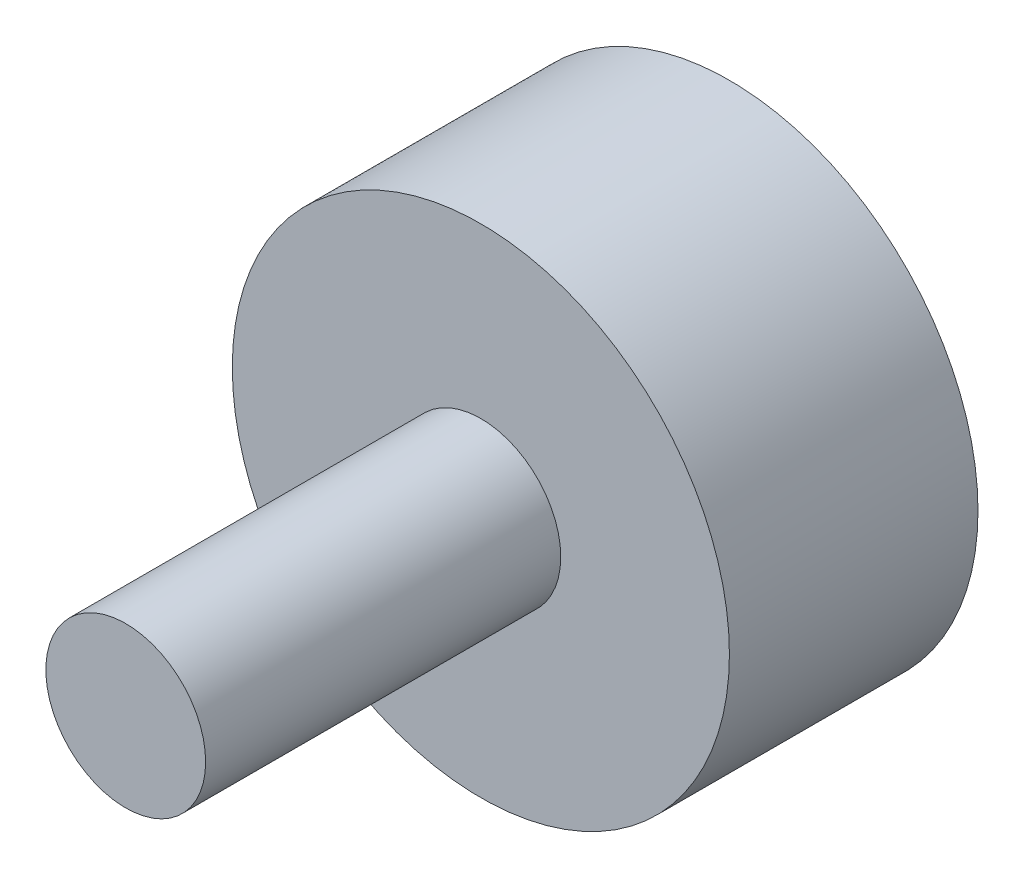
SolidWorks part; units mm, degrees
ref_plane "Front Plane" through (0, 0, 0) normal (0, 0, 1) x (1, 0, 0)
ref_plane "Top Plane" through (0, 0, 0) normal (0, 1, 0) x (1, 0, 0)
ref_plane "Right Plane" through (0, 0, 0) normal (1, 0, 0) x (0, 0, -1)
sketch "Sketch1" plane through (0, 0, 0) normal (0, 0, 1) x (1, 0, 0)
  circle A0 centre (0, 0) radius 7
  circle A1 centre (0, 0) radius 4
  dimension "D1" = 14
  dimension "D2" = 8
extrude "Boss-Extrude1" add sketch "Sketch1" along normal blind 5
sketch "Sketch2" plane through (0, 0, 5) normal (0, 0, 1) x (1, 0, 0)
  circle A0 centre (0, 0) radius 7
  dimension "D1" = 14
extrude "Boss-Extrude2" add sketch "Sketch2" along normal blind 2
sketch "Sketch3" plane through (0, 0, 7) normal (0, 0, 1) x (1, 0, 0)
  circle A0 centre (0, 0) radius 2.25
  dimension "D1" = 4.5
extrude "Boss-Extrude3" add sketch "Sketch3" along normal blind 10
thread "Thread1" pitch 1 method extrude profile "Thread Profile1" start angle 0, offset 0, length 0, pitch 1, diameter 8
ref_plane "Plane1" through (4, 0, 0) normal (0, -1, 0) x (1, 0, 0)
sketch "Thread Profile1" plane through (4, 0, 0) normal (0, -1, 0) x (1, 0, 0)
  line L0 (0, 0) -> (0, 1) construction
  line L11 (0, 0) -> (0, 0.875)
  line L12 (0, 0.875) -> (-0.5413, 0.5625)
  line L13 (-0.5413, 0.5625) -> (-0.5413, 0.3125)
  line L15 (-0.5413, 0.3125) -> (0, 0)
  line L17 (-0.5413, 0.4375) -> (0, 0.4375) construction
  point P2 (0, 0)
  dimension "Pitch" = 1
  dimension "Profile_Angle" = 60
  dimension "Profile_Land" = 0.25
  dimension "Profile_Height" = 0.5413
